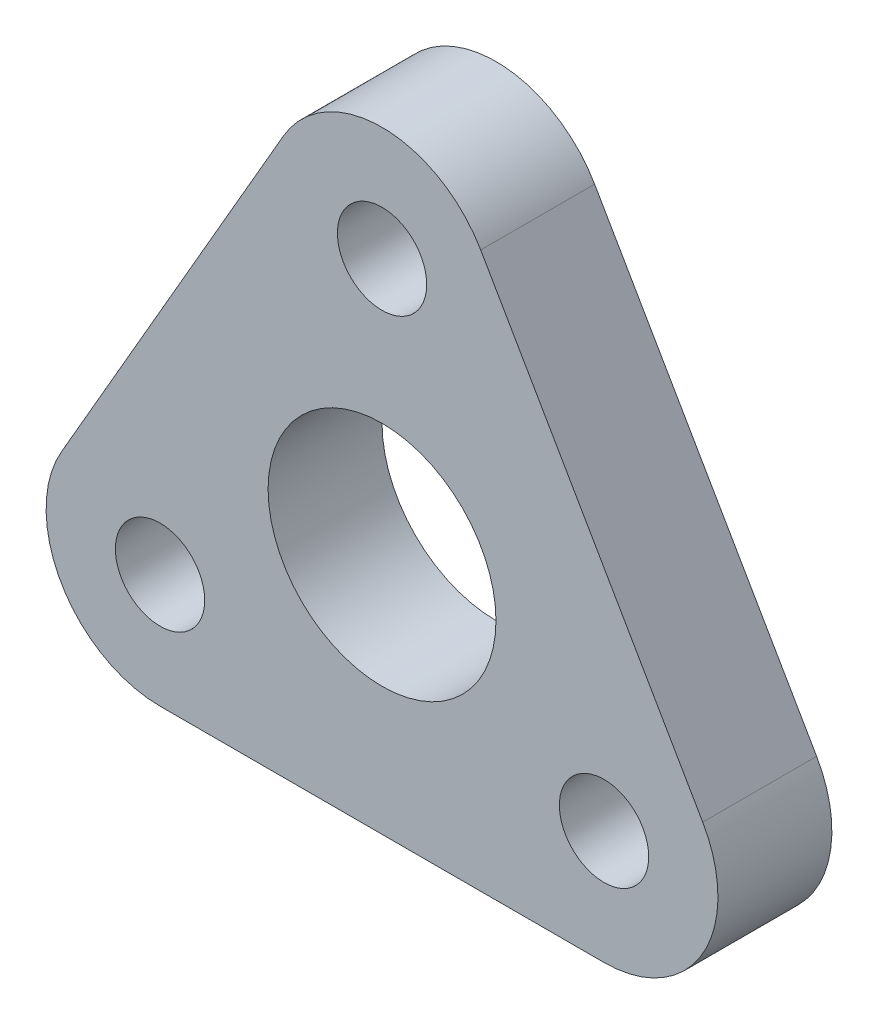
SolidWorks part; units mm, degrees
material "6061-T6 (SS)"
ref_plane "Front Plane" through (0, 0, 0) normal (0, 0, 1) x (1, 0, 0)
ref_plane "Top Plane" through (0, 0, 0) normal (0, 1, 0) x (1, 0, 0)
ref_plane "Right Plane" through (0, 0, 0) normal (1, 0, 0) x (0, 0, -1)
sketch "Sketch1" plane through (0, 0, 0) normal (0, 0, 1) x (1, 0, 0)
  line L3 (0, 14.2875) -> (12.3733, -7.1438) construction
  line L4 (12.3733, -7.1438) -> (-12.3733, -7.1438) construction
  line L5 (-12.3733, -7.1438) -> (0, 14.2875) construction
  line L6 (0, 26.9875) -> (23.3719, -13.4938)
  line L7 (23.3719, -13.4938) -> (-23.3719, -13.4938)
  line L8 (-23.3719, -13.4938) -> (0, 26.9875)
  circle A0 centre (0, 0) radius 6.35
  circle A1 centre (0, 14.2875) radius 2.4892
  circle A2 centre (12.3733, -7.1438) radius 2.4892
  circle A3 centre (-12.3733, -7.1438) radius 2.4892
  point P11 (0, 0)
  dimension "D1" = 12.7
  dimension "D2" = 4.9784
  dimension "D3" = 14.2875
  dimension "D5" = 6.35
  dimension "D4" = 3
extrude "Boss-Extrude1" add sketch "Sketch1" along normal blind 6.35
fillet "Fillet1" radius 6.35 3 edges at (23.3719, -13.4938, 3.175) (-23.3719, -13.4938, 3.175) (0, 26.9875, 3.175)
